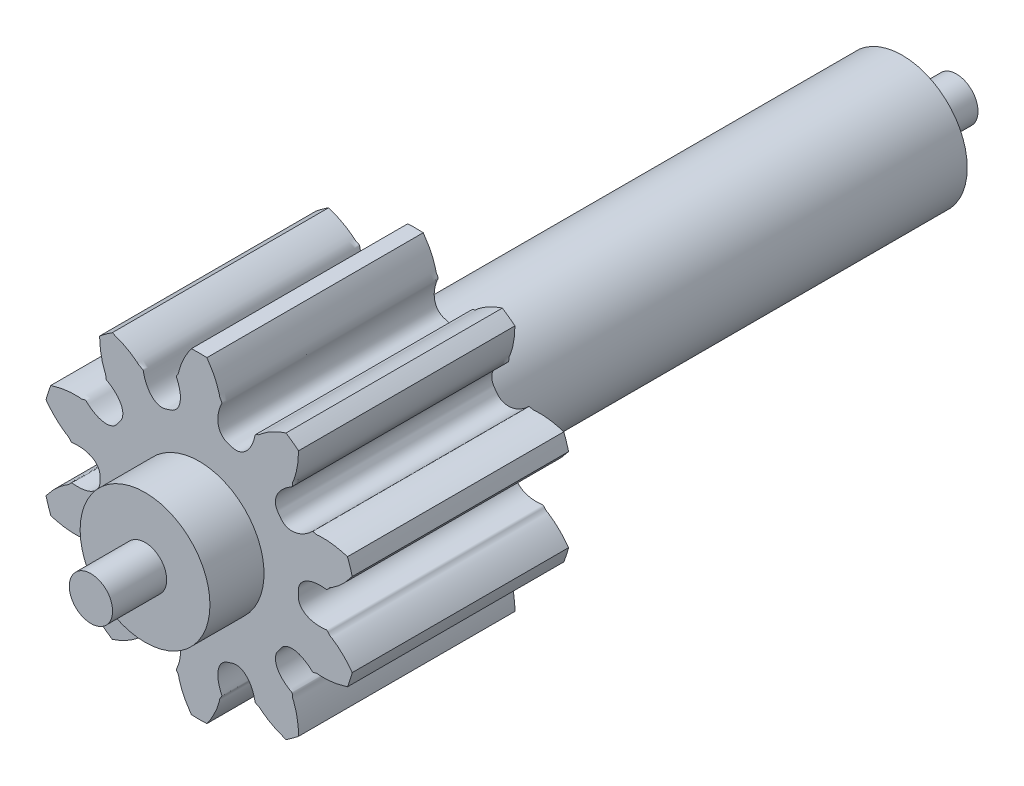
SolidWorks part; units mm, degrees
ref_plane "Alzado" through (0, 0, 0) normal (0, 0, 1) x (1, 0, 0)
ref_plane "Planta" through (0, 0, 0) normal (0, 1, 0) x (1, 0, 0)
ref_plane "Vista lateral" through (0, 0, 0) normal (1, 0, 0) x (0, 0, -1)
ref_axis "Eje1" through (0, 0, 55) along (0, 0, -1)
sketch "SketchRevolveEngranaje 10d" plane through (0, 0, 0) normal (1, 0, 0) x (0, 0, -1)
  line L0 (0, 0) -> (1, 0) construction
  line L1 (-0.5, 0) -> (-0.5, 0.7333)
  line L2 (-0.5, 0.7333) -> (0.5, 0.7333)
  line L3 (0.5, 0.7333) -> (0.5, 0)
  line L4 (0.5, 0) -> (-0.5, 0)
revolve "Engranaje 10d" add sketch "SketchRevolveEngranaje 10d" angle 360 about L0
sketch "SketchToothEngranaje 10d" plane through (0, 0, 0) normal (0, 0, 1) x (1, 0, 0)
  arc A0 (0.7123, 0.1985) -> (0.7123, -0.1985) centre (0, 0) cw
  spline S0 degree 3 poles (0.7123, -0.1985) (0.7054, -0.1888) (0.6947, -0.1749) (0.6798, -0.1579) (0.669, -0.1465) (0.6585, -0.1363) (0.6483, -0.1272) (0.6385, -0.1191) (0.6291, -0.1119) (0.6202, -0.1058) (0.612, -0.1001) (0.5994, -0.0948) (0.5932, -0.0786) (0.5808, -0.0818) (0.5744, -0.0821) (0.5679, -0.0825) (0.5616, -0.0826) (0.5555, -0.0826) (0.5495, -0.0824) (0.5436, -0.0819) (0.5379, -0.0813) (0.5323, -0.0805) (0.5268, -0.0795) (0.5215, -0.0783) (0.5163, -0.0769) (0.5113, -0.0753) (0.5064, -0.0735) (0.5017, -0.0715) (0.4971, -0.0693) (0.4927, -0.0669) (0.4884, -0.0642) (0.4843, -0.0613) (0.4803, -0.0581) (0.4765, -0.0546) (0.473, -0.0508) (0.4697, -0.0467) (0.4667, -0.0422) (0.464, -0.0373) (0.4618, -0.0322) (0.46, -0.0267) (0.4588, -0.0209) (0.4583, -0.0157) (0.4581, -0.0087) (0.4585, 0) (0.4581, 0.0087) (0.4583, 0.0157) (0.4588, 0.0209) (0.46, 0.0267) (0.4618, 0.0322) (0.464, 0.0373) (0.4667, 0.0422) (0.4697, 0.0467) (0.473, 0.0508) (0.4765, 0.0546) (0.4803, 0.0581) (0.4843, 0.0613) (0.4884, 0.0642) (0.4927, 0.0669) (0.4971, 0.0693) (0.5017, 0.0715) (0.5064, 0.0735) (0.5113, 0.0753) (0.5163, 0.0769) (0.5215, 0.0783) (0.5268, 0.0795) (0.5323, 0.0805) (0.5379, 0.0813) (0.5436, 0.0819) (0.5495, 0.0824) (0.5555, 0.0826) (0.5616, 0.0826) (0.5679, 0.0825) (0.5744, 0.0821) (0.5808, 0.0818) (0.5932, 0.0786) (0.5994, 0.0948) (0.612, 0.1001) (0.6202, 0.1058) (0.6291, 0.1119) (0.6385, 0.1191) (0.6483, 0.1272) (0.6585, 0.1363) (0.669, 0.1465) (0.6798, 0.1579) (0.6947, 0.1749) (0.7054, 0.1888) (0.7123, 0.1985) knots 0 0 0 0 0.051264 0.074872 0.097132 0.118042 0.137603 0.155815 0.172678 0.188193 0.202358 0.215174 0.246663 0.256263 0.265652 0.274833 0.283812 0.292594 0.301186 0.309594 0.317827 0.325893 0.333801 0.341564 0.349194 0.356705 0.364113 0.371436 0.378694 0.38591 0.393107 0.400314 0.40756 0.414873 0.422286 0.429827 0.437521 0.445387 0.453433 0.461657 0.470039 0.478544 0.484243 0.5 0.515757 0.521456 0.529961 0.538343 0.546567 0.554613 0.562479 0.570173 0.577714 0.585127 0.59244 0.599686 0.606893 0.61409 0.621306 0.628564 0.635887 0.643295 0.650806 0.658436 0.666199 0.674107 0.682173 0.690406 0.698814 0.707406 0.716188 0.725167 0.734348 0.743737 0.753337 0.784826 0.797642 0.811807 0.827322 0.844185 0.862397 0.881958 0.902868 0.925128 0.948736 1 1 1 1
extrude "ToothExtrudeCutEngranaje 10d" cut sketch "SketchToothEngranaje 10d" against normal blind 0.5 and the other way blind 0.5
pattern_circular "PatternEngranaje 10d" count 10 every 36 about axis through (0, 0, 55) along (0, 0, -1) of "ToothExtrudeCutEngranaje 10d"
sketch "AuxiliarySketchEngranaje 10d" plane through (0, 0, 0) normal (0, 0, 1) x (1, 0, 0)
  circle A0 centre (0, 0) radius 0.6111 construction
  circle A1 centre (0, 0) radius 0.5743 construction
  circle A2 centre (0, 0) radius 0.5981 construction
  circle A3 centre (0, 0) radius 0.7333 construction
  circle A4 centre (0, 0) radius 0.4583 construction
  dimension "PitchDiameter" = 1.2222
  dimension "BaseDiameter" = 1.1485
  dimension "FormDiameter" = 1.1962
  dimension "MajorDiameter" = 1.4667
  dimension "MinorDiameter" = 0.9167
sketch "Croquis1" plane through (0, 0, 0.5) normal (0, 0, 1) x (1, 0, 0)
  circle A0 centre (0, 0) radius 0.3
  dimension "D1" = 0.6
extrude "Saliente-Extruir1" add sketch "Croquis1" along normal blind 0.25
sketch "Croquis2" plane through (0, 0, 0.75) normal (0, 0, 1) x (1, 0, 0)
  circle A0 centre (0, 0) radius 0.1
  dimension "D1" = 0.2
extrude "Saliente-Extruir2" add sketch "Croquis2" along normal blind 0.25
sketch "Croquis3" plane through (0, 0, -0.5) normal (0, 0, -1) x (-1, 0, 0)
  circle A0 centre (0, 0) radius 0.3
  dimension "D1" = 0.6
extrude "Saliente-Extruir3" add sketch "Croquis3" along normal blind 2.25
sketch "Croquis4" plane through (0, 0, -2.75) normal (0, 0, -1) x (-1, 0, 0)
  circle A0 centre (0, 0) radius 0.1
  dimension "D1" = 0.2
extrude "Saliente-Extruir4" add sketch "Croquis4" along normal blind 0.25
